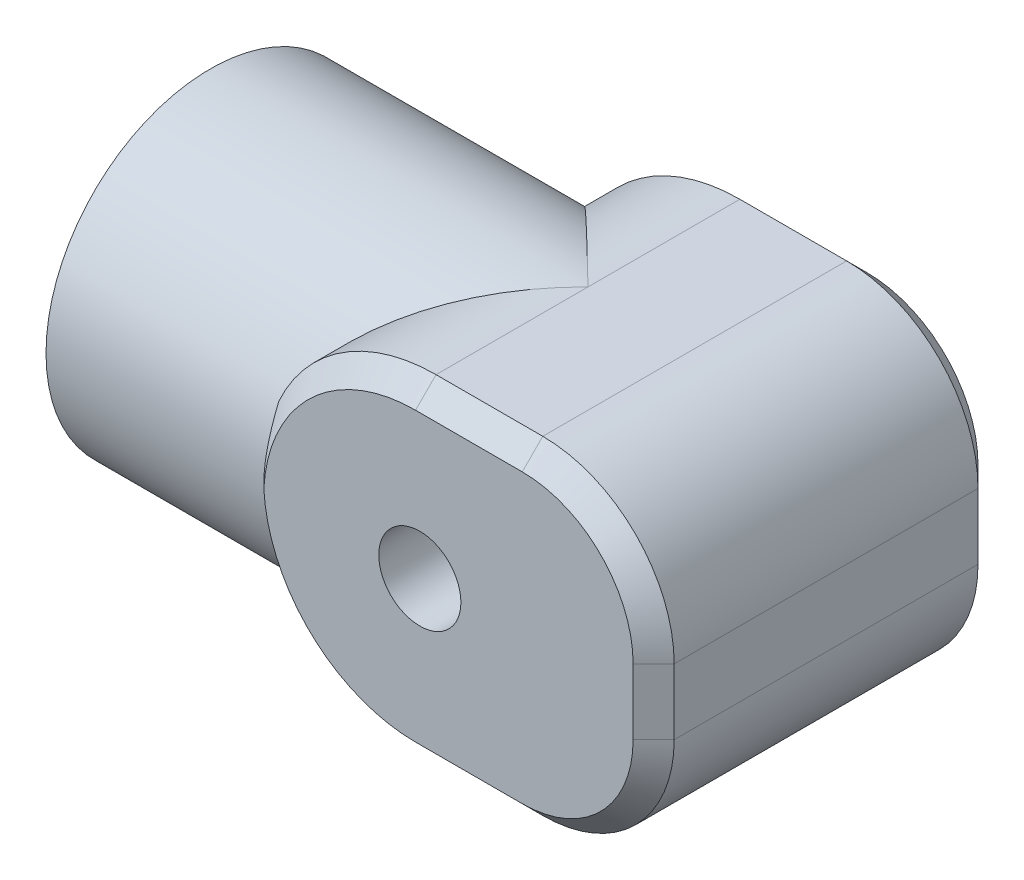
SolidWorks part; units mm, degrees
ref_plane "Front Plane" through (0, 0, 0) normal (0, 0, 1) x (1, 0, 0)
ref_plane "Top Plane" through (0, 0, 0) normal (0, 1, 0) x (1, 0, 0)
ref_plane "Right Plane" through (0, 0, 0) normal (1, 0, 0) x (0, 0, -1)
sketch "Sketch1" plane through (0, 0, 0) normal (0, 1, 0) x (1, 0, 0)
  line L1 (0, 0) -> (50, 0)
  line L2 (0, 0) -> (0, 42)
  line L3 (0, 42) -> (50, 42)
  line L4 (50, 0) -> (50, 42)
  dimension "D1" = 50
  dimension "D2" = 42
extrude "Boss-Extrude1" add sketch "Sketch1" along normal blind 40
ref_plane "Plane1" through (-25, 0, 0) normal (-1, 0, 0) x (0, 0, 1)
fillet "Fillet1" radius 21 2 edges at (0, 0, -21) (0, 40, -21)
sketch "Sketch2" plane through (-25, 0, 0) normal (-1, 0, 0) x (0, 0, 1)
  line L0 (0, 20) -> (-42, 20) construction
  circle A0 centre (-21, 20) radius 20
  dimension "D1" = 40
fillet "Fillet2" radius 16 2 edges at (50, 0, -21) (50, 40, -21)
extrude "Boss-Extrude2" add sketch "Sketch2" against normal up to next
chamfer "Chamfer1" distance 2.5 angle 45 14 edges at (27.5, 40, 0) (45.3137, 35.3137, 0) (6.5086, 34.1987, 0) (50, 20, 0) (6.5086, 5.8013, 0) (45.3137, 4.6863, 0) (27.5, 0, 0) (45.3137, 35.3137, -42) (27.5, 40, -42) (50, 20, -42) (6.5086, 34.1987, -42) (45.3137, 4.6863, -42) (6.5086, 5.8013, -42) (27.5, 0, -42)
sketch "Sketch3" plane through (0, 0, 0) normal (0, 0, 1) x (1, 0, 0)
  circle A0 centre (21.5257, 20) radius 5
  dimension "D1" = 10
  dimension "D2" = 20
extrude "Cut-Extrude1" cut sketch "Sketch3" against normal blind 10
sketch "Sketch4" plane through (-25, 0, 0) normal (-1, 0, 0) x (0, 0, 1)
  circle A0 centre (-21, 20) radius 5
  dimension "D1" = 10
extrude "Boss-Extrude3" add sketch "Sketch4" along normal blind 10
